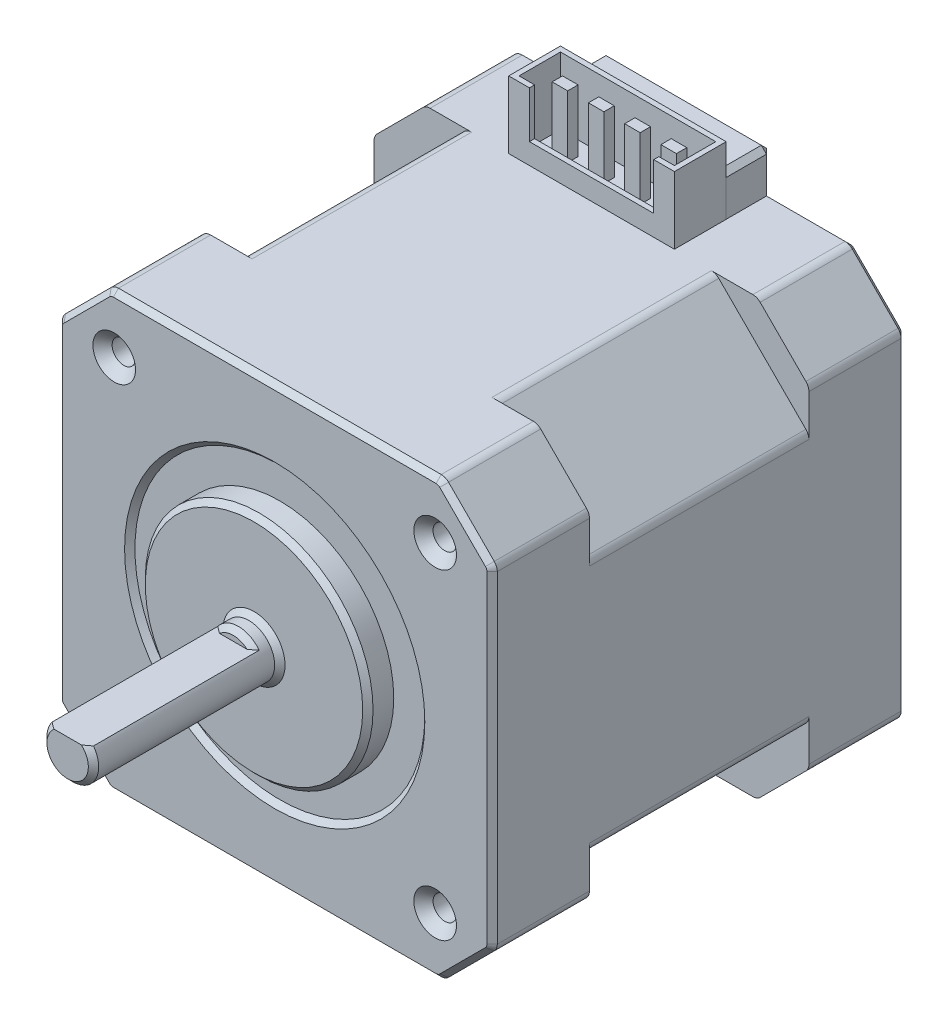
SolidWorks part; units mm, degrees
ref_plane "Front Plane" through (0, 0, 0) normal (0, 0, 1) x (1, 0, 0)
ref_plane "Top Plane" through (0, 0, 0) normal (0, 1, 0) x (1, 0, 0)
ref_plane "Right Plane" through (0, 0, 0) normal (1, 0, 0) x (0, 0, -1)
sketch "Sketch1" plane through (0, 0, 0) normal (0, 0, 1) x (1, 0, 0)
  line L1 (21, 21) -> (-21, 21)
  line L2 (21, 21) -> (21, -21)
  line L3 (21, -21) -> (-21, -21)
  line L4 (-21, 21) -> (-21, -21)
  point P0 (0, 0)
  dimension "D1" = 42
  dimension "D2" = 42
extrude "Boss-Extrude1" add sketch "Sketch1" along normal blind 9.4
chamfer "Chamfer1" distance 5 4 edges at (21, -21, 4.7) (-21, -21, 4.7) (-21, 21, 4.7) (21, 21, 4.7)
sketch "Sketch2" plane through (0, 0, 0) normal (0, 0, -1) x (-1, 0, 0)
  line L8 (-21, 16) -> (-21, -16)
  line L9 (-21, -16) -> (-16, -21)
  line L10 (-16, -21) -> (16, -21)
  line L11 (16, -21) -> (21, -16)
  line L12 (21, -16) -> (21, 16)
  line L13 (21, 16) -> (16, 21)
  line L14 (16, 21) -> (-16, 21)
  line L15 (-16, 21) -> (-21, 16)
  line L16 (-21, 16) -> (-21, -16)
  line L17 (-21, -16) -> (-16, -21)
  line L18 (-16, -21) -> (16, -21)
  line L19 (16, -21) -> (21, -16)
  line L20 (21, -16) -> (21, 16)
  line L21 (21, 16) -> (16, 21)
  line L22 (16, 21) -> (-16, 21)
  line L23 (-16, 21) -> (-21, 16)
  dimension "D1" = 0
sketch "Sketch3" plane through (0, 0, 9.4) normal (0, 0, 1) x (1, 0, 0)
  line L0 (-12, 21) -> (-21, 12)
  line L1 (21, 12) -> (12, 21)
  line L2 (12, -21) -> (21, -12)
  line L3 (-21, -12) -> (-12, -21)
  line L8 (-16, -21) -> (16, -21)
  line L9 (16, -21) -> (21, -16)
  line L10 (21, -16) -> (21, 16)
  line L11 (21, 16) -> (16, 21)
  line L12 (16, 21) -> (-16, 21)
  line L13 (-16, 21) -> (-21, 16)
  line L14 (-21, 16) -> (-21, -16)
  line L15 (-21, -16) -> (-16, -21)
  line L16 (-12, -21) -> (12, -21)
  line L18 (21, -12) -> (21, 12)
  line L20 (12, 21) -> (-12, 21)
  line L22 (-21, 12) -> (-21, -12)
  point P19 (0, 0)
  dimension "D3" = 9
  dimension "D4" = 9
  dimension "D1" = 0
  dimension "D5" = 4
extrude "Boss-Extrude3" add sketch "Sketch3" along normal blind 21.2
sketch "Sketch5" plane through (0, 0, 30.6) normal (0, 0, 1) x (1, 0, 0)
  line L0 (-16, 21) -> (16, 21) construction
  line L1 (-16, 21) -> (16, 21)
  line L2 (21, -16) -> (16, -21) construction
  line L3 (-16, -21) -> (-21, -16) construction
  line L4 (21, 21) -> (-21, 21)
  line L5 (-21, 21) -> (-21, -21)
  line L6 (-21, -21) -> (21, -21)
  line L7 (21, -21) -> (21, 21)
  line L8 (12, 21) -> (-12, 21)
  line L9 (-12, 21) -> (-21, 12)
  line L10 (-21, 12) -> (-21, -12)
  line L11 (-21, -12) -> (-12, -21)
  line L12 (-12, -21) -> (12, -21)
  line L13 (12, -21) -> (21, -12)
  line L14 (21, -12) -> (21, 12)
  line L15 (21, 12) -> (12, 21)
  line L16 (12, 21) -> (-12, 21)
  line L17 (-12, 21) -> (-21, 12)
  line L18 (-21, 12) -> (-21, -12)
  line L19 (-21, -12) -> (-12, -21)
  line L20 (-12, -21) -> (12, -21)
  line L21 (12, -21) -> (21, -12)
  line L22 (21, -12) -> (21, 12)
  line L23 (21, 12) -> (12, 21)
  line L24 (21, 21) -> (-21, 21)
  line L25 (-21, 21) -> (-21, -21)
  line L26 (-21, -21) -> (21, -21)
  line L27 (21, -21) -> (21, 21)
  line L28 (16, 21) -> (21, 16) construction
  line L29 (-21, 16) -> (-16, 21) construction
  line L30 (21, -16) -> (16, -21)
  line L31 (-16, -21) -> (-21, -16)
  line L32 (16, 21) -> (21, 16)
  line L33 (-21, 16) -> (-16, 21)
  line M13 (12, 21) -> (-12, 21)
  line M14 (-12, 21) -> (-21, 12)
  line M15 (-21, 12) -> (-21, -12)
  line M16 (-21, -12) -> (-12, -21)
  line M17 (-12, -21) -> (12, -21)
  line M18 (12, -21) -> (21, -12)
  line M19 (21, -12) -> (21, 12)
  line M20 (21, 12) -> (12, 21)
  dimension "D1" = 0
  dimension "D2" = 0
extrude "Boss-Extrude6" add sketch "Sketch5" along normal blind 9.4 contours M20 M13 M14 M15 M16 M17 M18 M19 | L33 L25 L1 M14 | L32 L1 L27 M20 | L30 L27 L26 M18 | L31 L26 L25 M16 region at (-17.4048, 17.4048, 30.6) region at (0, 0, 30.6) region at (17.4048, 17.4048, 30.6) region at (-17.4048, -17.4048, 30.6) region at (17.4048, -17.4048, 30.6)
sketch "Sketch6" plane through (0, 0, 0) normal (0, 0, -1) x (-1, 0, 0)
  line L0 (16, 21) -> (-16, 21) construction
  line L1 (-8.0005, 21) -> (7.9995, 21)
  line L2 (-8.0005, 21) -> (-8.0005, 25)
  line L3 (-8.0005, 25) -> (7.9995, 25)
  line L4 (7.9995, 21) -> (7.9995, 25)
  line L5 (0, 0) -> (0, 27.533) construction
  dimension "D1" = 16
  dimension "D2" = 4
extrude "Boss-Extrude7" add sketch "Sketch6" against normal blind 4.4
sketch "Sketch7" plane through (0, 21, 0) normal (0, 1, 0) x (1, 0, 0)
  line L1 (-7.9995, -4.4) -> (8.0058, -4.4)
  line L2 (-7.9995, -4.4) -> (-7.9995, -9.3985)
  line L3 (-7.9995, -9.3985) -> (8.0058, -9.3985)
  line L4 (8.0058, -4.4) -> (8.0058, -9.3985)
  line L6 (-7.4995, -8.8985) -> (7.5058, -8.8985)
  line L7 (7.5058, -4.9) -> (7.5058, -8.8985)
  line L8 (-7.4995, -4.9) -> (7.5058, -4.9)
  line L9 (-7.4995, -4.9) -> (-7.4995, -8.8985)
  dimension "D1" = 0.5
extrude "Boss-Extrude8" add sketch "Sketch7" along normal blind 6.5
sketch "Sketch8" plane through (0, 0, 9.3985) normal (0, 0, 1) x (1, 0, 0)
  line L0 (-5.9995, 25.5) -> (-5.9995, 29.3812)
  line L1 (-5.9995, 29.3812) -> (6.0058, 29.3812)
  line L2 (6.0058, 29.3812) -> (6.0058, 25.5)
  line L8 (-5.9995, 23) -> (6.0058, 23)
  line L9 (6.0058, 23) -> (6.0058, 25.5)
  line L10 (6.0058, 25.5) -> (-5.9995, 25.5)
  line L11 (-5.9995, 25.5) -> (-5.9995, 23)
  line L12 (-5.9995, 23) -> (6.0058, 23)
  line L13 (6.0058, 23) -> (6.0058, 25.5)
  line L15 (-5.9995, 25.5) -> (-5.9995, 23)
  dimension "D1" = 2
extrude "Cut-Extrude1" cut sketch "Sketch8" against normal up to surface (0.5 mm away) up to face at (0.0031, 24.25, 8.8985)
sketch "Sketch9" plane through (0, 21, 0) normal (0, 1, 0) x (1, 0, 0)
  line L0 (7.5058, -4.9) -> (-7.4995, -4.9) construction
  line L1 (-5.8995, -6.3) -> (-4.3995, -6.3)
  line L2 (-5.8995, -6.3) -> (-5.8995, -7.3)
  line L3 (-5.8995, -7.3) -> (-4.3995, -7.3)
  line L4 (-4.3995, -6.3) -> (-4.3995, -7.3)
  line L6 (-7.4995, -4.9) -> (-7.4995, -8.8985) construction
  line L7 (-2.3995, -6.3) -> (-0.8995, -6.3)
  line L8 (-0.8995, -6.3) -> (-0.8995, -7.3)
  line L9 (-2.3995, -7.3) -> (-0.8995, -7.3)
  line L10 (-2.3995, -6.3) -> (-2.3995, -7.3)
  line L11 (1.1005, -6.3) -> (2.6005, -6.3)
  line L12 (2.6005, -6.3) -> (2.6005, -7.3)
  line L13 (1.1005, -7.3) -> (2.6005, -7.3)
  line L14 (1.1005, -6.3) -> (1.1005, -7.3)
  line L15 (4.6005, -6.3) -> (6.1005, -6.3)
  line L16 (6.1005, -6.3) -> (6.1005, -7.3)
  line L17 (4.6005, -7.3) -> (6.1005, -7.3)
  line L18 (4.6005, -6.3) -> (4.6005, -7.3)
  dimension "D1" = 1
  dimension "D2" = 1.5
  dimension "D3" = 1.4
  dimension "D4" = 1.6
  dimension "D5" = 4
extrude "Boss-Extrude9" add sketch "Sketch9" along normal blind 6
sketch "Sketch10" plane through (0, 0, 40) normal (0, 0, 1) x (1, 0, 0)
  circle A0 centre (0, 0) radius 11
  dimension "D1" = 22
extrude "Boss-Extrude10" add sketch "Sketch10" along normal blind 2
sketch "Sketch11" plane through (0, 0, 42) normal (0, 0, 1) x (1, 0, 0)
  circle A0 centre (0, 0) radius 2.5
  dimension "D1" = 5
extrude "Boss-Extrude11" add sketch "Sketch11" along normal blind 18
sketch "Sketch12" plane through (0, 0, 60) normal (0, 0, 1) x (1, 0, 0)
  line L0 (-2, 1.5) -> (2, 1.5)
  circle A0 centre (0, 0) radius 2.5 construction
  dimension "D1" = 1.5
extrude "Cut-Extrude3" cut sketch "Sketch12" against normal blind 16 and the other way through all
sketch "Sketch13" plane through (0, 0, 40) normal (0, 0, 1) x (1, 0, 0)
  circle A0 centre (0, 0) radius 14
  circle A1 centre (0, 0) radius 11 construction
  circle A2 centre (0, 0) radius 11
  dimension "D1" = 28
extrude "Cut-Extrude4" cut sketch "Sketch13" against normal blind 0.5
sketch "Sketch16" plane through (0, 0, 40) normal (0, 0, 1) x (1, 0, 0)
  point P0 (-15.5, 15.5)
  dimension "D1" = 15.5
  dimension "D2" = 15.5
hole_wizard "#4-40 Tapped Hole1" positions "Sketch16" profile "Sketch15" tap size "#4-40" standard "ANSI Inch"
sketch "Sketch15" plane through (-15.5, 15.5, 40) normal (1, 0, 0) x (0, -1, 0)
  line L0 (0, 0) -> (0, 9.1792)
  line L1 (0, 9.1792) -> (1.1303, 8.5)
  line L2 (1.1303, 8.5) -> (1.1303, 0.9271)
  line L3 (1.1303, 0.9271) -> (2.0574, 0)
  line L5 (2.0574, 0) -> (0, 0)
  line L6 (-1.1303, 0.9271) -> (-2.0574, 0) construction
  line L10 (0, 9.1792) -> (-1.1303, 8.5) construction
  line L11 (0, -6.35) -> (0, 107.95) construction
  dimension "Tap Drill Dia." = 2.2606
  dimension "Tap Drill Depth" = 8.5
  dimension "Near C'Sink Dia." = 4.1148
  dimension "Near C'Sink Angle" = 90
  dimension "Drill Angle" = 118
cosmetic thread "Hole Thread1" parameters "D1"=6, "D2"=2.8448
pattern_circular "CirPattern2" count 4 over 360 about axis through (0, 0, 40) along (0, 0, 1) of "#4-40 Tapped Hole1"
cosmetic thread "Hole Thread5" parameters "D1"=6, "D2"=2.8448
cosmetic thread "Hole Thread6" parameters "D1"=6, "D2"=2.8448
cosmetic thread "Hole Thread7" parameters "D1"=6, "D2"=2.8448
chamfer "Chamfer3" distance 0.5 angle 45 5 edges at (11, 0, 42) (2.5, 0, 42) (14, 0, 40) (0, -2.5, 60) (0, 2.5, 44)
fillet "Fillet1" radius 1 24 edges at (-16, 21, 4.7) (-12, 21, 20) (-16, 21, 35.3) (-21, 16, 4.7) (-21, 12, 20) (-21, 16, 35.3) (-21, -16, 4.7) (-21, -12, 20) (-21, -16, 35.3) (-16, -21, 4.7) (-12, -21, 20) (-16, -21, 35.3) (16, -21, 4.7) (12, -21, 20) (16, -21, 35.3) (21, -16, 4.7) (21, -12, 20) (21, -16, 35.3) (16, 21, 4.7) (21, 16, 4.7) (12, 21, 20) (21, 12, 20) (21, 16, 35.3) (16, 21, 35.3)
chamfer "Chamfer4" distance 0.5 angle 45 37 edges at (18.5, 18.5, 0) (-11.7927, 21, 0) (-18.5, 18.5, 0) (-18.5, -18.5, 0) (-21, 0, 0) (0, -21, 0) (18.5, -18.5, 0) (21, 0, 0) (-18.5, -18.5, 40) (18.5, -18.5, 40) (0, -21, 40) (21, 0, 40) (18.5, 18.5, 40) (-21, 0, 40) (-18.5, 18.5, 40) (15.9685, -20.9239, 40) (-15.9685, -20.9239, 40) (20.9239, -15.9685, 40) (-20.9239, -15.9685, 40) (20.9239, 15.9685, 40) (-20.9239, 15.9685, 40) (15.9685, 20.9239, 40) (-15.9685, 20.9239, 40) (0, 21, 40) (-15.9685, 20.9239, 0) (-20.9239, 15.9685, 0) (-20.9239, -15.9685, 0) (-15.9685, -20.9239, 0) (15.9685, -20.9239, 0) (20.9239, -15.9685, 0) (20.9239, 15.9685, 0) (15.9685, 20.9239, 0) (11.7931, 21, 0) (8.0005, 23, 0) (-7.9995, 25, 2.2) (0.0005, 25, 0) (8.0005, 25, 2.2)
